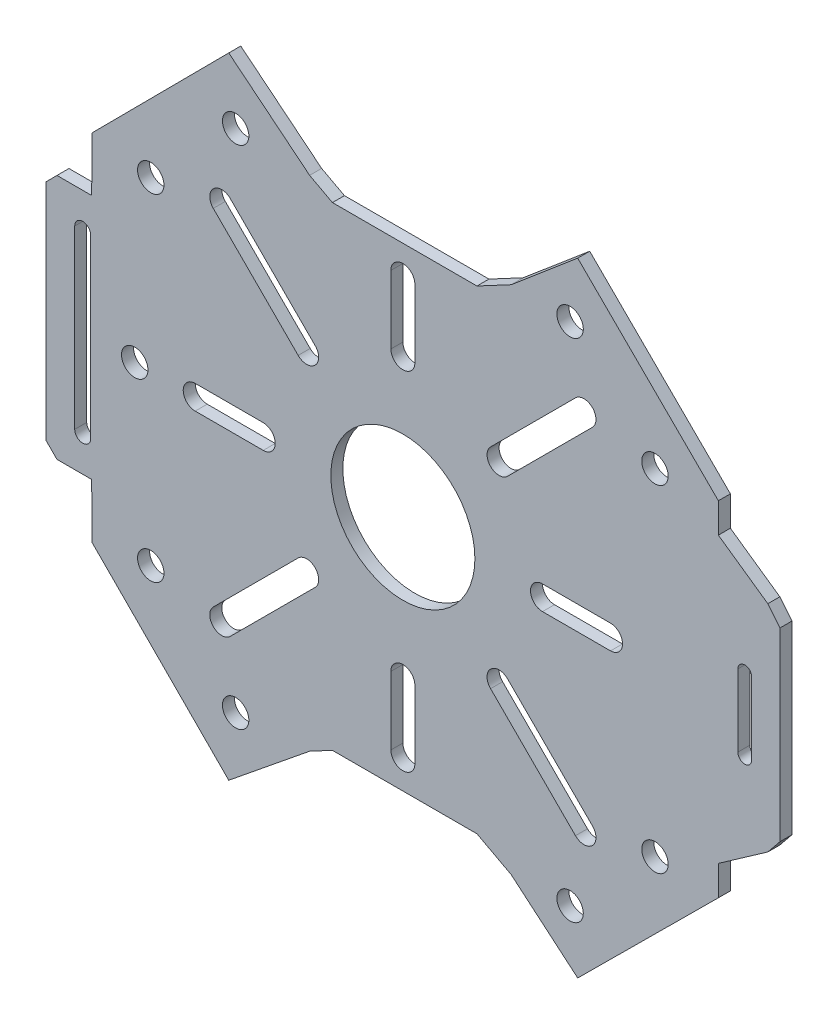
SolidWorks part; units mm, degrees
ref_plane "前视基准面" through (0, 0, 0) normal (0, 0, 1) x (1, 0, 0)
ref_plane "上视基准面" through (0, 0, 0) normal (0, 1, 0) x (1, 0, 0)
ref_plane "右视基准面" through (0, 0, 0) normal (1, 0, 0) x (0, 0, -1)
sketch "Upper_board" plane through (0, 0, 0) normal (0, 0, 1) x (1, 0, 0)
  line L0 (146.4713, -65.3649) -> (146.4713, 899.9684) construction
  line L1 (-20.8934, 31.6066) -> (-31.5, 21) construction
  line L2 (0, 0) -> (0, 48.26) construction
  line L3 (0, 0) -> (79.7901, 0) construction
  line L4 (0, 29.6377) -> (9.2582, 29.6377)
  line L5 (9.2582, 29.6377) -> (13.5301, 31.9144)
  line L6 (13.5301, 31.9144) -> (21.8452, 38.9473)
  line L7 (21.8452, 38.9473) -> (39.4221, 21.4832)
  line L8 (39.4221, 21.4832) -> (39.4221, 17.7594)
  line L9 (39.4221, 17.7594) -> (45.6027, 13.4317)
  line L10 (45.6027, 13.4317) -> (47.1171, 11.5642)
  line L11 (47.1171, 11.5642) -> (47.1171, -11.5642)
  line L12 (45.6027, -13.4317) -> (47.1171, -11.5642)
  line L13 (39.4221, -17.7594) -> (45.6027, -13.4317)
  line L14 (39.4221, -21.4832) -> (39.4221, -17.7594)
  line L15 (21.8452, -38.9473) -> (39.4221, -21.4832)
  line L16 (13.5301, -31.9144) -> (21.8452, -38.9473)
  line L17 (9.2582, -29.6377) -> (13.5301, -31.9144)
  line L18 (0, -29.6377) -> (9.2582, -29.6377)
  line L19 (0, 29.6377) -> (-8.8004, 29.6377)
  line L20 (-8.8004, 29.6377) -> (-11.6488, 31.1557)
  line L21 (-11.6488, 31.1557) -> (-21.7549, 39.351)
  line L22 (-21.7549, 39.351) -> (-38.8505, 22.145)
  line L23 (-38.8505, 22.145) -> (-38.8781, 15.3642)
  line L24 (-38.8781, 15.3642) -> (-43.2196, 15.3642)
  line L25 (-43.2196, 15.3642) -> (-44.5853, 13.9896)
  line L26 (-44.5853, 13.9896) -> (-44.5853, -13.9896)
  line L27 (-8.8004, -29.6377) -> (-11.6488, -31.1557)
  line L28 (0, -29.6377) -> (-8.8004, -29.6377)
  line L29 (-11.6488, -31.1557) -> (-21.7549, -39.351)
  line L30 (-21.7549, -39.351) -> (-38.8505, -22.145)
  line L31 (-38.8505, -22.145) -> (-38.8781, -15.3642)
  line L32 (-38.8781, -15.3642) -> (-43.2196, -15.3642)
  line L33 (-43.2196, -15.3642) -> (-44.5853, -13.9896)
  line L34 (-22.627, 22.627) -> (-12.0212, 12.0212) construction
  line L35 (-21.5663, 23.6876) -> (-10.9606, 13.0819)
  line L36 (-23.6876, 21.5663) -> (-13.0819, 10.9606)
  line L37 (0, 17.4457) -> (0, 25.9457) construction
  line L38 (-1.5, 17.4457) -> (-1.5, 25.9457)
  line L39 (1.5, 17.4457) -> (1.5, 25.9457)
  line L40 (0, -17.4457) -> (0, -25.9457) construction
  line L41 (-1.5, -17.4457) -> (-1.5, -25.9457)
  line L42 (1.5, -17.4457) -> (1.5, -25.9457)
  line L43 (0, 0) -> (-17.3241, 17.3241) construction
  line L44 (-17.4457, 0) -> (-25.9457, 0) construction
  line L45 (-17.4457, 1.5) -> (-25.9457, 1.5)
  line L46 (-17.4457, -1.5) -> (-25.9457, -1.5)
  line L47 (17.4457, 0) -> (25.9457, 0) construction
  line L48 (17.4457, 1.5) -> (25.9457, 1.5)
  line L49 (17.4457, -1.5) -> (25.9457, -1.5)
  line L50 (-22.627, -22.627) -> (-12.0212, -12.0212) construction
  line L51 (-21.5663, -23.6876) -> (-10.9606, -13.0819)
  line L52 (-23.6876, -21.5663) -> (-13.0819, -10.9606)
  line L53 (22.627, 22.627) -> (12.0212, 12.0212) construction
  line L54 (21.5663, 23.6876) -> (10.9606, 13.0819)
  line L55 (23.6876, 21.5663) -> (13.0819, 10.9606)
  line L56 (22.627, -22.627) -> (12.0212, -12.0212) construction
  line L57 (21.5663, -23.6876) -> (10.9606, -13.0819)
  line L58 (23.6876, -21.5663) -> (13.0819, -10.9606)
  line L59 (-40, -11) -> (-40, 11) construction
  line L60 (-41, -11) -> (-41, 11)
  line L61 (-39, -11) -> (-39, 11)
  line L62 (42.7214, -4.5) -> (42.7214, 4.5) construction
  line L63 (41.8554, -4.5) -> (41.8554, 4.5)
  line L64 (43.5874, -4.5) -> (43.5874, 4.5)
  circle A0 centre (0, 0) radius 9
  circle A3 centre (-20.8934, 31.6066) radius 1.65
  circle A4 centre (-31.5, 21) radius 1.65
  circle A5 centre (-33.5, 0) radius 1.65
  circle A6 centre (20.8934, 31.6066) radius 1.65
  circle A7 centre (31.5, 21) radius 1.65
  circle A8 centre (-20.8934, -31.6066) radius 1.65
  circle A9 centre (-31.5, -21) radius 1.65
  circle A10 centre (20.8934, -31.6066) radius 1.65
  circle A11 centre (31.5, -21) radius 1.65
  arc A12 (-21.5663, 23.6876) -> (-23.6876, 21.5663) centre (-22.627, 22.627) ccw
  arc A13 (-13.0819, 10.9606) -> (-10.9606, 13.0819) centre (-12.0212, 12.0212) ccw
  arc A14 (-1.5, 17.4457) -> (1.5, 17.4457) centre (0, 17.4457) ccw
  arc A15 (1.5, 25.9457) -> (-1.5, 25.9457) centre (0, 25.9457) ccw
  arc A16 (-1.5, -17.4457) -> (1.5, -17.4457) centre (0, -17.4457) cw
  arc A17 (1.5, -25.9457) -> (-1.5, -25.9457) centre (0, -25.9457) cw
  arc A18 (-17.4457, 1.5) -> (-17.4457, -1.5) centre (-17.4457, 0) cw
  arc A19 (-25.9457, -1.5) -> (-25.9457, 1.5) centre (-25.9457, 0) cw
  arc A20 (17.4457, 1.5) -> (17.4457, -1.5) centre (17.4457, 0) ccw
  arc A21 (25.9457, -1.5) -> (25.9457, 1.5) centre (25.9457, 0) ccw
  arc A22 (-21.5663, -23.6876) -> (-23.6876, -21.5663) centre (-22.627, -22.627) cw
  arc A23 (-13.0819, -10.9606) -> (-10.9606, -13.0819) centre (-12.0212, -12.0212) cw
  arc A24 (21.5663, 23.6876) -> (23.6876, 21.5663) centre (22.627, 22.627) cw
  arc A25 (13.0819, 10.9606) -> (10.9606, 13.0819) centre (12.0212, 12.0212) cw
  arc A26 (21.5663, -23.6876) -> (23.6876, -21.5663) centre (22.627, -22.627) ccw
  arc A27 (13.0819, -10.9606) -> (10.9606, -13.0819) centre (12.0212, -12.0212) ccw
  arc A28 (-41, -11) -> (-39, -11) centre (-40, -11) ccw
  arc A29 (-39, 11) -> (-41, 11) centre (-40, 11) ccw
  arc A30 (41.8554, -4.5) -> (43.5874, -4.5) centre (42.7214, -4.5) ccw
  arc A31 (43.5874, 4.5) -> (41.8554, 4.5) centre (42.7214, 4.5) ccw
  point P37 (47.1171, 0)
  point P52 (-17.3241, 17.3241)
  point P59 (-44.5853, 0)
  point P66 (0, 21.6957)
  point P78 (0, -21.6957)
  point P84 (-21.6957, 0)
  point P91 (21.6957, 0)
  point P98 (-17.3241, -17.3241)
  point P105 (17.3241, 17.3241)
  point P112 (17.3241, -17.3241)
  point P119 (-40, 0)
  point P124 (42.7214, 0)
  point P131 (0, 0)
  point P133 (32.4239, 0)
  dimension "D1" = 21
  dimension "D2" = 31.5
  dimension "D3" = 3.3
  dimension "D6" = 3.3
  dimension "D9" = 45
  dimension "D11" = 0
  dimension "D12" = 40
  dimension "D16" = 3.3
  dimension "D4" = 33.5
  dimension "D5" = 15
  dimension "D7" = 29.6377
  dimension "D8" = 47.1171
  dimension "D10" = 24.5
  dimension "D13" = 0
  dimension "D14" = 21
  dimension "D15" = 45
extrude "凸台-拉伸1" add sketch "Upper_board" along normal blind 1.5
